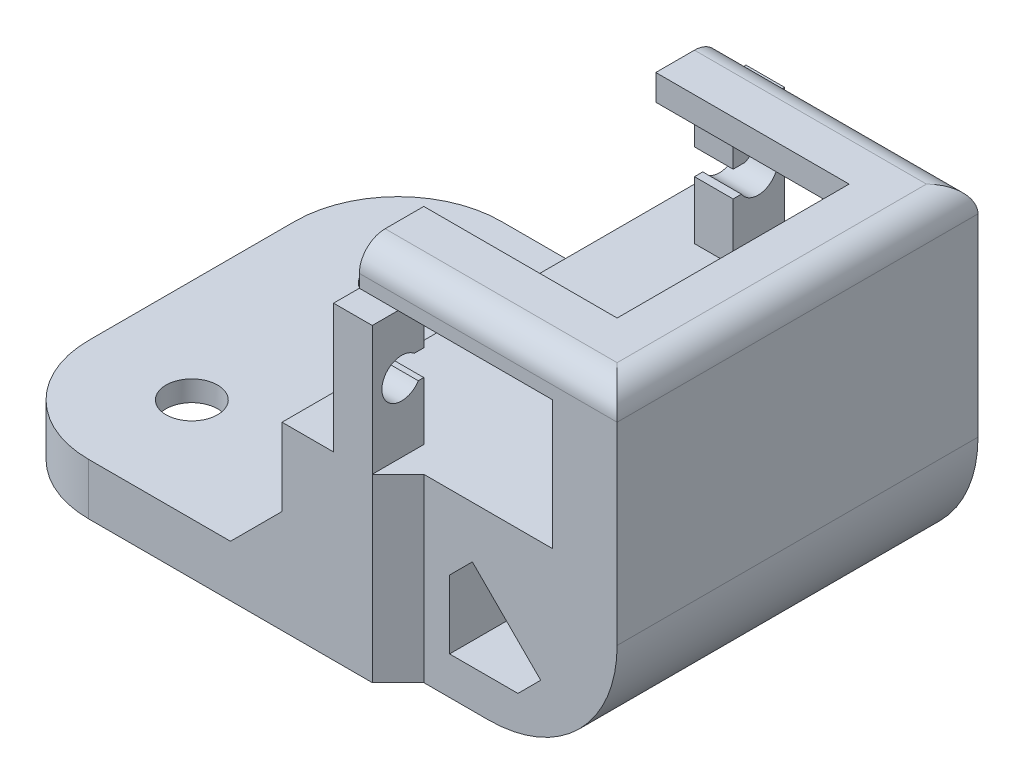
SolidWorks part; units mm, degrees
ref_plane "Front Plane" through (0, 0, 0) normal (0, 0, 1) x (1, 0, 0)
ref_plane "Top Plane" through (0, 0, 0) normal (0, 1, 0) x (1, 0, 0)
ref_plane "Right Plane" through (0, 0, 0) normal (1, 0, 0) x (0, 0, -1)
sketch "Sketch1" plane through (0, 0, 0) normal (0, 1, 0) x (1, 0, 0)
  line L1 (0, 0) -> (59.69, 0)
  line L2 (0, 0) -> (0, 50.8)
  line L3 (0, 50.8) -> (59.69, 50.8)
  line L4 (59.69, 0) -> (59.69, 50.8)
  dimension "D1" = 50.8
  dimension "D2" = 59.69
extrude "Boss-Extrude1" add sketch "Sketch1" along normal blind 5.08
sketch "Sketch2" plane through (0, 5.08, 0) normal (0, 1, 0) x (1, 0, 0)
  line L1 (29.21, 50.8) -> (29.21, 0)
  line L4 (0, 50.8) -> (0, 0)
  line L5 (0, 0) -> (59.69, 0)
  line L6 (59.69, 0) -> (59.69, 50.8)
  line L7 (59.69, 50.8) -> (0, 50.8)
  line L8 (0, 50.8) -> (0, 0)
  line L9 (0, 0) -> (59.69, 0)
  line L10 (59.69, 0) -> (59.69, 50.8)
  line L11 (59.69, 50.8) -> (0, 50.8)
  line M12 (0, 0) -> (59.69, 0)
  line M13 (59.69, 0) -> (59.69, 50.8)
  line M14 (59.69, 50.8) -> (0, 50.8)
  dimension "D4" = 30.48
  dimension "D1" = 0
extrude "Boss-Extrude2" add sketch "Sketch2" along normal blind 12.7 contours L1 M12 M13 M14 region at (44.45, 5.08, -25.4)
sketch "Sketch3" plane through (0, 17.78, 0) normal (0, 1, 0) x (1, 0, 0)
  line L5 (0, 0) -> (29.21, 0) construction
  line L6 (59.69, 50.8) -> (21.59, 50.8)
  line L7 (59.69, 50.8) -> (59.69, 0)
  line L8 (59.69, 0) -> (21.59, 0)
  line L9 (21.59, 50.8) -> (21.59, 0)
  line L11 (59.69, 43.18) -> (34.29, 43.18)
  line L12 (59.69, 43.18) -> (59.69, 7.62)
  line L13 (59.69, 7.62) -> (34.29, 7.62)
  line L14 (34.29, 43.18) -> (34.29, 7.62)
  dimension "D1" = 38.1
  dimension "D2" = 25.4
  dimension "D3" = 35.56
  dimension "D4" = 7.62
extrude "Boss-Extrude3" add sketch "Sketch3" along normal blind 16.51 contours L11 L14 L13 L12
sketch "Sketch5" plane through (34.29, 0, 0) normal (-1, 0, 0) x (0, 0, 1)
  line L0 (-43.18, 17.78) -> (-7.62, 17.78) construction
  line L1 (-40.64, 17.78) -> (-10.16, 17.78)
  line L2 (-40.64, 17.78) -> (-40.64, 31.75)
  line L3 (-40.64, 31.75) -> (-10.16, 31.75)
  line L4 (-10.16, 17.78) -> (-10.16, 31.75)
  line L5 (-43.18, 34.29) -> (-43.18, 17.78) construction
  dimension "D1" = 30.48
  dimension "D2" = 13.97
  dimension "D3" = 2.54
extrude "Cut-Extrude1" cut sketch "Sketch5" against normal blind 20.32
sketch "Sketch6" plane through (0, 0, -7.62) normal (0, 0, 1) x (1, 0, 0)
  line L0 (59.69, 34.29) -> (59.69, 17.78) construction
  line L1 (49.53, 28.448) -> (53.34, 28.448)
  line L2 (49.53, 28.448) -> (49.53, 20.828)
  line L3 (49.53, 20.828) -> (53.34, 20.828)
  line L4 (53.34, 28.448) -> (53.34, 20.828)
  line L5 (29.21, 17.78) -> (59.69, 17.78) construction
  dimension "D1" = 6.35
  dimension "D2" = 3.048
  dimension "D3" = 7.62
  dimension "D4" = 3.81
ref_plane "Plane1" through (0, 0, -25.4) normal (0, 0, -1) x (-1, 0, 0)
fillet "Fillet2" radius 2.54 3 edges at (59.69, 34.29, -25.4) (46.99, 34.29, -43.18) (46.99, 34.29, -7.62)
fillet "Fillet3" radius 12.7 1 edges at (59.69, 0, -25.4)
sketch "Sketch8" plane through (0, 0, -7.62) normal (0, 0, 1) x (1, 0, 0)
  line L0 (34.29, 31.75) -> (34.29, 17.78) construction
  line L1 (34.29, 30.48) -> (45.72, 30.48)
  line L2 (34.29, 30.48) -> (34.29, 17.78)
  line L3 (34.29, 17.78) -> (45.72, 17.78)
  line L4 (45.72, 30.48) -> (45.72, 17.78)
  line L5 (59.69, 17.78) -> (34.29, 17.78) construction
  dimension "D1" = 11.43
  dimension "D2" = 0
  dimension "D3" = 12.7
sketch "Sketch10" plane through (34.29, 0, 0) normal (-1, 0, 0) x (0, 0, 1)
  line L0 (-50.8, 17.78) -> (0, 17.78) construction
  line L1 (-10.16, 31.75) -> (-8.5725, 31.75)
  line L2 (-10.16, 31.75) -> (-10.16, 17.78)
  line L3 (-10.16, 17.78) -> (-8.5725, 17.78)
  line L4 (-8.5725, 31.75) -> (-8.5725, 17.78)
  circle A0 centre (-8.5725, 24.765) radius 1.1846
  dimension "D1" = 1.5875
sketch "Sketch11" plane through (0, 0, -7.62) normal (0, 0, 1) x (1, 0, 0)
  line L0 (59.69, 17.78) -> (34.29, 17.78) construction
  line L2 (34.29, 30.48) -> (45.72, 30.48) construction
  line L3 (34.29, 17.78) -> (45.72, 17.78) construction
  line L4 (59.69, 17.78) -> (34.29, 17.78)
  line L6 (34.29, 30.48) -> (45.72, 30.48)
  line L7 (34.29, 17.78) -> (45.72, 17.78)
  line L8 (34.29, 30.48) -> (34.29, 17.78) construction
  line L10 (38.1, 30.48) -> (38.1, 17.78)
  line L11 (38.1, 17.78) -> (53.34, 17.78)
  line L12 (53.34, 30.48) -> (53.34, 17.78)
  line L13 (45.72, 30.48) -> (53.34, 30.48)
  dimension "D1" = 15.24
  dimension "D2" = 3.81
extrude "Cut-Extrude4" cut sketch "Sketch11" against normal blind 48.514 contours L12 L10 L7 L4 region at (45.72, 24.13, -7.62)
sketch "Sketch12" plane through (0, 0, -7.62) normal (0, 0, 1) x (1, 0, 0)
  line L0 (34.29, 17.78) -> (45.72, 17.78) construction
  line L1 (38.1, 30.48) -> (38.1, 17.78) construction
  line L2 (34.29, 30.48) -> (34.29, 17.78) construction
  line L3 (34.29, 30.48) -> (45.72, 30.48) construction
  line L4 (34.29, 17.78) -> (45.72, 17.78)
  line L5 (38.1, 30.48) -> (38.1, 17.78)
  line L6 (34.29, 30.48) -> (34.29, 17.78)
  line L7 (34.29, 30.48) -> (45.72, 30.48)
  line M10 (34.29, 31.75) -> (34.29, 17.78)
  line M11 (34.29, 17.78) -> (38.1, 17.78)
  line M12 (38.1, 17.78) -> (38.1, 30.48)
extrude "Boss-Extrude5" add sketch "Sketch12" along normal blind 2.54 contours L7 M10 M11 M12 region at (36.195, 24.13, -7.62)
sketch "Sketch13" plane through (34.29, 0, 0) normal (-1, 0, 0) x (0, 0, 1)
  line L0 (-10.16, 31.75) -> (-10.16, 17.78) construction
  line L1 (-10.16, 26.035) -> (-6.985, 26.035)
  line L2 (-10.16, 26.035) -> (-10.16, 23.495)
  line L3 (-10.16, 23.495) -> (-6.985, 23.495)
  line L4 (-6.985, 26.035) -> (-6.985, 23.495)
  line L5 (-10.16, 31.75) -> (-40.64, 31.75) construction
  dimension "D1" = 2.54
  dimension "D2" = 3.175
  dimension "D3" = 5.715
extrude "Cut-Extrude5" cut sketch "Sketch13" against normal blind 4.318 contours L1 L4 L3 L2
mirror "Mirror6" about plane through (0, 0, -25.4) normal (0, 0, -1) of "Cut-Extrude5", "Boss-Extrude5"
sketch "Sketch14" plane through (0, 5.08, 0) normal (0, 1, 0) x (1, 0, 0)
  line L7 (29.21, 50.8) -> (0, 50.8)
  line L8 (0, 50.8) -> (0, 0)
  line L9 (0, 0) -> (29.21, 0)
  line L11 (29.21, 0) -> (29.21, 50.8)
  line L13 (29.21, 50.8) -> (0, 50.8)
  line L14 (0, 50.8) -> (0, 0)
  line L15 (0, 0) -> (29.21, 0)
  line L17 (29.21, 0) -> (29.21, 50.8)
  arc A0 (9.51, 16.5919) -> (9.51, 13.8881) centre (10.16, 15.24) ccw construction
  arc A1 (9.51, 16.5919) -> (9.51, 13.8881) centre (10.16, 15.24) ccw
  arc A2 (7.7618, 36.6362) -> (12.5582, 36.6362) centre (10.16, 35.24) ccw construction
  arc A3 (12.5582, 37.8438) -> (7.7618, 37.8438) centre (10.16, 39.24) ccw construction
  arc A8 (10.81, 13.8881) -> (10.81, 16.5919) centre (10.16, 15.24) ccw construction
  arc A9 (7.7618, 36.6362) -> (12.5582, 36.6362) centre (10.16, 35.24) ccw
  arc A10 (12.5582, 37.8438) -> (7.7618, 37.8438) centre (10.16, 39.24) ccw
  arc A11 (10.81, 13.8881) -> (10.81, 16.5919) centre (10.16, 15.24) ccw
  circle A12 centre (10.16, 15.24) radius 2.54
  circle A13 centre (10.16, 39.24) radius 2.54
  circle A14 centre (10.16, 35.24) radius 2.54
  dimension "D1" = 0
extrude "Cut-Extrude6" cut sketch "Sketch14" against normal blind 14.732 contours A14 A13 | A12 | A14 region at (10.16, 5.08, -15.24) region at (10.16, 5.08, -39.4969)
sketch "Sketch15" plane through (0, 0, 0) normal (0, -1, 0) x (1, 0, 0)
  line L0 (6.81, -39.24) -> (6.81, -27.24) construction
  line L1 (13.51, -27.24) -> (13.51, -39.24) construction
  line L2 (6.81, -39.24) -> (6.81, -27.24)
  line L3 (13.51, -27.24) -> (13.51, -39.24)
  line L4 (6.556, -39.24) -> (6.556, -27.24)
  line L5 (13.764, -27.24) -> (13.764, -39.24)
  arc A0 (9.51, -7.8686) -> (7.56, -8.3118) centre (10.16, -15.24) ccw construction
  arc A1 (7.56, -8.3118) -> (3.2318, -12.64) centre (10.16, -15.24) ccw construction
  arc A2 (3.2318, -12.64) -> (9.51, -22.6114) centre (10.16, -15.24) ccw construction
  arc A3 (4.7333, -20.3697) -> (4.6204, -20.2029) centre (-5.5928, -27.24) ccw construction
  arc A4 (4.8886, -20.6091) -> (4.7792, -20.4392) centre (-5.5928, -27.24) ccw construction
  arc A5 (4.9758, -20.7489) -> (4.8886, -20.6091) centre (-5.5928, -27.24) ccw construction
  arc A6 (5.094, -20.9455) -> (4.9758, -20.7489) centre (-5.5928, -27.24) ccw construction
  arc A7 (6.81, -27.24) -> (5.2097, -21.1461) centre (-5.5928, -27.24) ccw construction
  arc A8 (6.81, -39.24) -> (13.51, -39.24) centre (10.16, -39.24) ccw construction
  arc A9 (14.044, -23.64) -> (13.51, -27.24) centre (25.9128, -27.24) ccw construction
  arc A10 (16.0466, -19.7242) -> (14.044, -23.64) centre (25.9128, -27.24) ccw construction
  arc A11 (16.0466, -19.7242) -> (17.0882, -17.84) centre (10.16, -15.24) ccw construction
  arc A12 (17.0882, -17.84) -> (10.81, -7.8686) centre (10.16, -15.24) ccw construction
  arc A13 (9.51, -7.8686) -> (7.56, -8.3118) centre (10.16, -15.24) ccw
  arc A14 (7.56, -8.3118) -> (3.2318, -12.64) centre (10.16, -15.24) ccw
  arc A15 (3.2318, -12.64) -> (9.51, -22.6114) centre (10.16, -15.24) ccw
  arc A16 (4.7333, -20.3697) -> (4.2734, -19.7242) centre (-5.5928, -27.24) ccw
  arc A17 (4.8886, -20.6091) -> (4.7333, -20.3697) centre (-5.5928, -27.24) ccw
  arc A18 (4.9758, -20.7489) -> (4.8886, -20.6091) centre (-5.5928, -27.24) ccw
  arc A19 (5.2097, -21.1461) -> (4.9758, -20.7489) centre (-5.5928, -27.24) ccw
  arc A20 (6.81, -27.24) -> (5.2097, -21.1461) centre (-5.5928, -27.24) ccw
  arc A21 (6.81, -39.24) -> (13.51, -39.24) centre (10.16, -39.24) ccw
  arc A22 (14.044, -23.64) -> (13.51, -27.24) centre (25.9128, -27.24) ccw
  arc A23 (16.0466, -19.7242) -> (14.044, -23.64) centre (25.9128, -27.24) ccw
  arc A24 (16.0466, -19.7242) -> (17.0882, -17.84) centre (10.16, -15.24) ccw
  arc A25 (17.0882, -17.84) -> (10.81, -7.8686) centre (10.16, -15.24) ccw
  circle A26 centre (10.16, -15.24) radius 7.4
  arc A27 (4.5218, -20.5104) -> (4.0714, -19.8781) centre (-5.5928, -27.24) ccw
  arc A28 (4.674, -20.7449) -> (4.5218, -20.5104) centre (-5.5928, -27.24) ccw
  arc A29 (4.7594, -20.8819) -> (4.674, -20.7449) centre (-5.5928, -27.24) ccw
  arc A30 (4.9885, -21.2709) -> (4.7594, -20.8819) centre (-5.5928, -27.24) ccw
  arc A31 (6.556, -27.24) -> (4.9885, -21.2709) centre (-5.5928, -27.24) ccw
  arc A32 (6.556, -39.24) -> (13.764, -39.24) centre (10.16, -39.24) ccw
  arc A33 (14.287, -23.7137) -> (13.764, -27.24) centre (25.9128, -27.24) ccw
  arc A34 (16.2486, -19.8781) -> (14.287, -23.7137) centre (25.9128, -27.24) ccw
  arc A35 (16.2486, -19.8781) -> (17.326, -17.9292) centre (10.16, -15.24) ccw
  arc A36 (17.326, -17.9292) -> (10.8323, -7.6156) centre (10.16, -15.24) ccw
  circle A37 centre (10.16, -15.24) radius 7.654
  circle M2 centre (10.16, -15.24) radius 2.54
  arc M3 (11.7258, -37.24) -> (8.5942, -37.24) centre (10.16, -39.24) cw
  arc M4 (8.5942, -37.24) -> (11.7258, -37.24) centre (10.16, -35.24) cw
  dimension "D1" = 0.254
  dimension "D2" = 0.254
extrude "Cut-Extrude7" cut sketch "Sketch15" against normal blind 3.048 contours A25 A26 A13 A14 A15 A24 M2 | A23 A37 A35 A36 A19 A18 A17 A16 A15 A14 A13 A26 A25 A24 | A37 A19 A20 L2 A21 L3 A22 A23 M4 M3 | A37 A23 A22 L3 A21 L2 A20 A19 A27 A28 A29 A30 A31 L4 A32 L5 A33 A34 | A19 A37 A23 A26 A15 A16 A17 A18 region at (10.16, 0, -42.616) region at (10.16, 0, -29.8193) region at (4.588, 0, -20.4578) region at (5.1597, 0, -20.8171) region at (13.0653, 0, -21.8176)
sketch "Sketch16" plane through (34.29, 0, 0) normal (-1, 0, 0) x (0, 0, 1)
  circle A0 centre (-7.9729, 24.538) radius 2.2 construction
  circle A1 centre (-43.0996, 24.538) radius 2.2 construction
  circle A2 centre (-7.9729, 24.538) radius 2.2
  circle A3 centre (-43.0996, 24.538) radius 2.2
  circle A4 centre (-7.9729, 24.538) radius 1.946
  circle A5 centre (-43.0996, 24.538) radius 1.946
  line M3 (-40.64, 23.495) -> (-43.815, 23.495)
  line M4 (-43.815, 23.495) -> (-43.815, 26.035)
  line M5 (-43.815, 26.035) -> (-40.64, 26.035)
  line M9 (-10.16, 26.035) -> (-6.985, 26.035)
  line M10 (-6.985, 26.035) -> (-6.985, 23.495)
  line M11 (-6.985, 23.495) -> (-10.16, 23.495)
  dimension "D1" = 0.254
  dimension "D2" = 0.254
extrude "Cut-Extrude8" cut sketch "Sketch16" against normal blind 10.16 contours A5 M5 M3 M4 | A5 M3 M5 M4 | A4 M11 M9 M10 | A4 M9 M11 M10 region at (34.29, 24.7382, -8.3743) region at (34.29, 26.2517, -7.1686) region at (34.29, 26.0879, -42.8356) region at (34.29, 24.7352, -42.5613)
sketch "Sketch19" plane through (0, 17.78, 0) normal (0, 1, 0) x (1, 0, 0)
  line L0 (59.69, 0) -> (59.69, 7.62) construction
  line L1 (59.69, 43.18) -> (-2.8098, 43.18)
  line L2 (59.69, 43.18) -> (59.69, 54.4896)
  line L3 (59.69, 54.4896) -> (-2.8098, 54.4896)
  line L4 (-2.8098, 43.18) -> (-2.8098, 54.4896)
  line L5 (59.69, 7.62) -> (-8.8873, 7.62)
  line L6 (59.69, 7.62) -> (59.69, -5.0166)
  line L7 (59.69, -5.0166) -> (-8.8873, -5.0166)
  line L8 (-8.8873, 7.62) -> (-8.8873, -5.0166)
  line L10 (34.29, 45.72) -> (-2.8098, 45.72)
  line L11 (34.29, 45.72) -> (34.29, 43.18)
  line L12 (34.29, 43.18) -> (-2.8098, 43.18)
  line L13 (-2.8098, 45.72) -> (-2.8098, 43.18)
  line L14 (34.29, 5.08) -> (-8.8873, 5.08)
  line L15 (34.29, 5.08) -> (34.29, 7.62)
  line L16 (34.29, 7.62) -> (-8.8873, 7.62)
  line L17 (-8.8873, 5.08) -> (-8.8873, 7.62)
  line M1 (34.29, 45.72) -> (38.1, 45.72)
  line M2 (38.1, 45.72) -> (38.1, 40.64)
  line M4 (34.29, 40.64) -> (34.29, 45.72)
  line M6 (53.34, 43.18) -> (59.69, 43.18)
  line M7 (59.69, 43.18) -> (59.69, 50.8)
  line M8 (59.69, 50.8) -> (29.21, 50.8)
  line M10 (29.21, 50.8) -> (29.21, 0)
  line M12 (29.21, 0) -> (59.69, 0)
  line M13 (59.69, 0) -> (59.69, 7.62)
  line M14 (59.69, 7.62) -> (53.34, 7.62)
  line M19 (38.1, 5.08) -> (34.29, 5.08)
  line M20 (34.29, 5.08) -> (34.29, 10.16)
  line M22 (38.1, 10.16) -> (38.1, 5.08)
extrude "Cut-Extrude9" cut sketch "Sketch19" against normal blind 29.464 contours L5 L8 L7 L6 M12 M10 | L4 L1 L2 L3 M10 M8 | L1 M6 M7 M8 M10 M4 M1 M2 | L5 M14 M22 M19 M20 M10 M12 M13 region at (45.6125, 17.78, -47.2635) region at (22.1365, 17.78, -50.8312) region at (19.9145, 17.78, 0.6908) region at (45.6125, 17.78, -3.5365)
chamfer "Chamfer8" distance 2.54 2 edges at (38.1, 8.89, -43.18) (38.1, 8.89, -7.62)
chamfer "Chamfer9" distance 5.08 angle 45 1 edges at (29.21, 5.08, -25.4)
sketch "Sketch20" plane through (34.29, 0, 0) normal (-1, 0, 0) x (0, 0, 1)
  line L0 (-10.16, 31.75) -> (-40.64, 31.75) construction
  line L1 (-36.83, 31.75) -> (-13.97, 31.75)
  line L2 (-36.83, 31.75) -> (-36.83, 34.29)
  line L3 (-36.83, 34.29) -> (-13.97, 34.29)
  line L4 (-13.97, 31.75) -> (-13.97, 34.29)
  line L5 (-40.64, 34.29) -> (-10.16, 34.29) construction
  line L6 (-40.64, 31.75) -> (-40.64, 26.035) construction
  line L7 (-10.16, 26.035) -> (-10.16, 31.75) construction
  dimension "D1" = 3.81
  dimension "D2" = 3.81
extrude "Cut-Extrude10" cut sketch "Sketch20" against normal blind 19.05
fillet "Fillet4" radius 10.16 2 edges at (0, 2.54, -5.08) (0, 2.54, -45.72)
sketch "Sketch21" plane through (0, 0, -7.62) normal (0, 0, 1) x (1, 0, 0)
  line L0 (43.18, 10.4549) -> (49.9152, 3.7197)
  line L1 (45.4251, 12.7) -> (52.1603, 5.9648)
  line L2 (45.4251, 12.7) -> (43.18, 10.4549)
  line L3 (52.1603, 5.9648) -> (49.9152, 3.7197)
  line L5 (53.34, 17.78) -> (40.64, 17.78) construction
  line L6 (40.64, 17.78) -> (40.64, 0) construction
  line L8 (43.18, 10.4549) -> (49.9152, 10.4549)
  line L9 (43.18, 10.4549) -> (43.18, 3.7197)
  line L10 (43.18, 3.7197) -> (49.9152, 3.7197)
  line L11 (49.9152, 10.4549) -> (49.9152, 3.7197)
  dimension "D1" = 90
  dimension "D2" = 3.175
  dimension "D4" = 9.525
  dimension "D5" = 5.08
  dimension "D6" = 2.54
extrude "Cut-Extrude11" cut sketch "Sketch21" against normal blind 45.212 contours L9 L10 L0 | L2 L8 L1 | L11 L1 L8 L0 | L1 L11 L3 region at (47.483, 8.0228, -7.62) region at (45.4251, 11.2033, -7.62) region at (45.4251, 5.9648, -7.62) region at (50.6635, 5.9648, -7.62)
